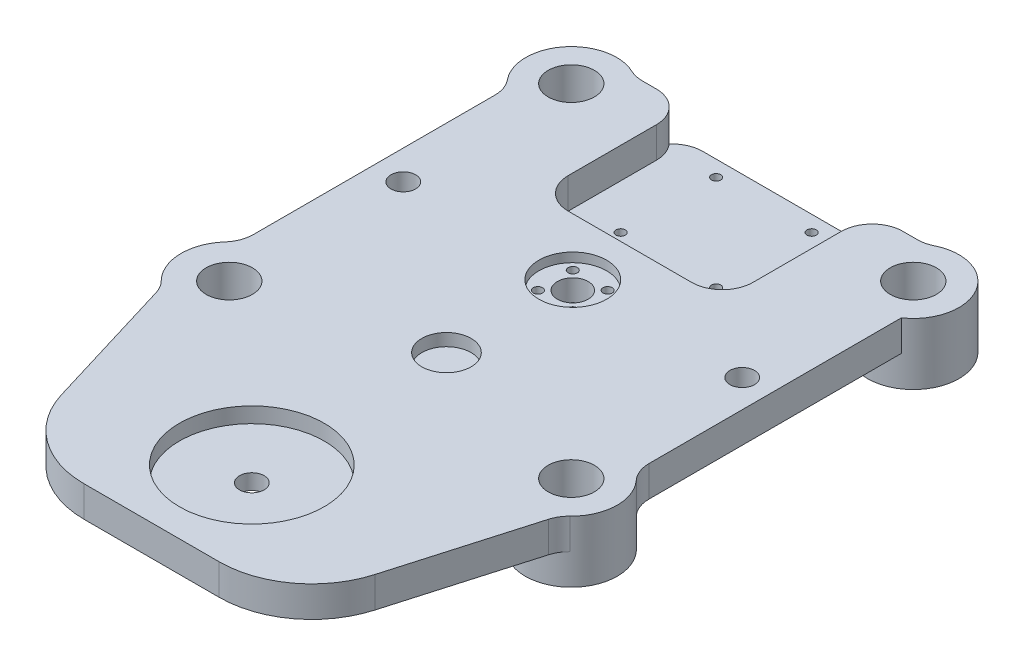
SolidWorks part; units mm, degrees
ref_plane "Front Plane" through (0, 0, 0) normal (0, 0, 1) x (1, 0, 0)
ref_plane "Top Plane" through (0, 0, 0) normal (0, 1, 0) x (1, 0, 0)
ref_plane "Right Plane" through (0, 0, 0) normal (1, 0, 0) x (0, 0, -1)
sketch "Sketch1" plane through (0, 0, 0) normal (0, 1, 0) x (1, 0, 0)
  line L0 (-55.3435, 80.7701) -> (55.6565, 80.7701) construction
  line L1 (-47.2225, 93.074) -> (47.3428, 93.074)
  line L2 (-64.5152, 69.2281) -> (-64.5152, -17.5957)
  line L4 (64.0417, 68.5147) -> (64.0417, -17.8733)
  line L5 (0.1565, -45.5027) -> (0.1565, -78.0027) construction
  line L6 (0.1565, -78.0027) -> (0.1565, -110.7506) construction
  line L7 (55.6565, 80.7701) -> (55.6565, -30.2299) construction
  line L8 (-55.3435, 80.7701) -> (-55.3435, -30.2299) construction
  line L9 (-55.3435, -30.2299) -> (55.6565, -30.2299) construction
  line L15 (-55.3435, -45.8423) -> (55.6565, -45.1631) construction
  line L20 (-44.1665, -110.7506) -> (44.4795, -110.7506)
  line L21 (-64.7902, -42.6599) -> (-44.1665, -110.7506)
  line L22 (44.4795, -110.7506) -> (64.2297, -42.4569)
  arc A0 (-47.2225, 93.074) -> (-64.5152, 69.2281) centre (-55.3435, 80.7701) ccw
  arc A1 (64.0417, 68.5147) -> (47.3428, 93.074) centre (55.6565, 80.7701) ccw
  circle A2 centre (-55.3435, 80.7701) radius 7.5
  circle A3 centre (55.6565, 80.7701) radius 7.5
  arc A4 (-64.5152, -17.5957) -> (-64.7902, -42.6599) centre (-55.3435, -30.2299) ccw
  arc A5 (64.2297, -42.4569) -> (64.0417, -17.8733) centre (55.6565, -30.2299) ccw
  circle A6 centre (-55.3435, -30.2299) radius 7.5
  circle A7 centre (55.6565, -30.2299) radius 7.5
  arc A9 (-64.7902, -42.6599) -> (-64.5152, -17.5957) centre (-55.3435, -30.2299) ccw construction
  arc A10 (64.0417, -17.8733) -> (64.2297, -42.4569) centre (55.6565, -30.2299) ccw construction
  point P0 (0, 0)
  point P29 (0.1565, -110.7506)
extrude "Boss-Extrude1" add sketch "Sketch1" along normal blind 20
sketch "Sketch2" plane through (0, 20, 0) normal (0, 1, 0) x (1, 0, 0)
  line L1 (-15.5, 87.9354) -> (15.5, 87.9354) construction
  line L2 (-15.5, 87.9354) -> (-15.5, 56.9354) construction
  line L3 (-15.5, 56.9354) -> (15.5, 56.9354) construction
  line L4 (15.5, 87.9354) -> (15.5, 56.9354) construction
  line L5 (-15.5, 87.9354) -> (15.5, 56.9354) construction
  line L6 (-15.5, 56.9354) -> (15.5, 87.9354) construction
  circle A0 centre (-15.5, 87.9354) radius 1.5
  circle A1 centre (15.5, 87.9354) radius 1.5
  circle A2 centre (-15.5, 56.9354) radius 1.5
  circle A3 centre (15.5, 56.9354) radius 1.5
  point P0 (0, 72.4354)
extrude "Cut-Extrude1" cut sketch "Sketch2" against normal blind 20
sketch "Sketch4" plane through (0, 20, 0) normal (0, 1, 0) x (1, 0, 0)
  line L1 (-55.3435, 80.7701) -> (55.6565, 80.7701) construction
  line L2 (-55.3435, 80.7701) -> (-55.3435, -30.2299) construction
  line L3 (-55.3435, -30.2299) -> (55.6565, -30.2299) construction
  line L4 (55.6565, 80.7701) -> (55.6565, -30.2299) construction
  circle A0 centre (0, 25.9114) radius 5
extrude "Cut-Extrude2" cut sketch "Sketch4" against normal blind 20
sketch "Sketch5" plane through (0, 20, 0) normal (0, 1, 0) x (1, 0, 0)
  circle A0 centre (0, 25.9114) radius 11
extrude "Cut-Extrude3" cut sketch "Sketch5" against normal blind 3
sketch "Sketch6" plane through (0, 17, 0) normal (0, 1, 0) x (1, 0, 0)
  line L1 (-5.6569, 31.5682) -> (5.6569, 31.5682) construction
  line L2 (-5.6569, 31.5682) -> (-5.6569, 20.2545) construction
  line L3 (-5.6569, 20.2545) -> (5.6569, 20.2545) construction
  line L4 (5.6569, 31.5682) -> (5.6569, 20.2545) construction
  line L5 (-5.6569, 31.5682) -> (5.6569, 20.2545) construction
  line L6 (-5.6569, 20.2545) -> (5.6569, 31.5682) construction
  circle A0 centre (-5.6569, 31.5682) radius 1.5
  circle A1 centre (5.6569, 31.5682) radius 1.5
  circle A2 centre (5.6569, 20.2545) radius 1.5
  circle A3 centre (-5.6569, 20.2545) radius 1.5
  point P0 (0, 25.9114)
extrude "Cut-Extrude4" cut sketch "Sketch6" against normal through all
sketch "Sketch7" plane through (0, 20, 0) normal (0, 1, 0) x (1, 0, 0)
  circle A0 centre (0, -15.077) radius 8
extrude "Cut-Extrude5" cut sketch "Sketch7" against normal blind 4
fillet "Fillet3" radius 30 2 edges at (44.4795, 10, 110.7506) (-44.1665, 10, 110.7506)
fillet "Fillet4" radius 10 2 edges at (64.2297, 10, 42.4569) (-64.7902, 10, 42.6599)
sketch "Sketch9" plane through (0, 20, 0) normal (0, 1, 0) x (1, 0, 0)
  line L0 (-21.9072, -110.7506) -> (21.926, -110.7506) construction
  circle A0 centre (0, -78.2506) radius 23.5
  dimension "D1" = 32.5
extrude "Cut-Extrude6" cut sketch "Sketch9" against normal blind 5
sketch "Sketch10" plane through (0, 15, 0) normal (0, 1, 0) x (1, 0, 0)
  circle A0 centre (0, -78.2506) radius 4
extrude "Cut-Extrude7" cut sketch "Sketch10" against normal through all
sketch "Sketch11" plane through (0, 20, 0) normal (0, 1, 0) x (1, 0, 0)
  line L0 (-30, 44.4354) -> (30, 44.4354)
  line L1 (-15.5, 56.9354) -> (15.5, 87.9354) construction
  line L2 (-30, 44.4354) -> (-30, 114.4354)
  line L3 (-30, 114.4354) -> (30, 114.4354)
  line L4 (30, 114.4354) -> (30, 44.4354)
  point P3 (0, 44.4354)
  point P8 (0, 72.4354)
  dimension "D1" = 28
extrude "Cut-Extrude8" cut sketch "Sketch11" against normal blind 10
fillet "Fillet5" radius 10 2 edges at (30, 15, -44.4354) (-30, 15, -44.4354)
sketch "Sketch12" plane through (0, 0, 0) normal (0, -1, 0) x (1, 0, 0)
  line L0 (-55, -25.9114) -> (55, -25.9114) construction
  circle A0 centre (-55, -25.9114) radius 4 construction
  circle A1 centre (55, -25.9114) radius 4 construction
  circle A2 centre (-55, -25.9114) radius 12
  circle A3 centre (55, -25.9114) radius 12
  point P4 (0, -25.9114)
extrude "Cut-Extrude9" cut sketch "Sketch12" against normal blind 10
fillet "Fillet6" radius 10 4 edges at (64.0417, 5, -33.801) (64.0417, 5, -18.0217) (-64.5152, 5, -33.2231) (-64.5152, 5, -18.5997)
sketch "Sketch13" plane through (0, 10, 0) normal (0, -1, 0) x (1, 0, 0)
  circle A0 centre (-55, -25.9114) radius 4
  circle A1 centre (55, -25.9114) radius 4
extrude "Cut-Extrude10" cut sketch "Sketch13" against normal through all
sketch "Sketch14" plane through (0, 0, 0) normal (0, -1, 0) x (1, 0, 0)
  line L0 (-15.5, -56.9354) -> (15.5, -87.9354) construction
  line L1 (-35, -39.4354) -> (35, -39.4354)
  line L2 (-35, -39.4354) -> (-35, -93.074)
  line L3 (35, -93.074) -> (47.3428, -93.074)
  line L4 (-16.9351, -101.3096) -> (-16.7194, -101.3096)
  line L5 (35, -39.4354) -> (35, -93.074)
  line L8 (64.0417, -68.5147) -> (64.0417, -47.8905)
  line L9 (64.0417, -3.9323) -> (64.0417, 17.8733)
  line L10 (63.3869, 45.371) -> (50.7451, 89.0849)
  line L11 (21.926, 110.7506) -> (-21.9072, 110.7506)
  line L12 (-50.6191, 89.447) -> (-63.9757, 45.3491)
  line L13 (-64.5152, 17.5957) -> (-64.5152, -3.9167)
  line L14 (-64.5152, -47.906) -> (-64.5152, -69.2281)
  line L15 (-47.2225, -93.074) -> (47.3428, -93.074)
  line L16 (64.0417, -68.5147) -> (64.0417, -47.8905)
  line L17 (64.0417, -3.9323) -> (64.0417, 17.8733)
  line L18 (63.3869, 45.371) -> (50.7451, 89.0849)
  line L19 (21.926, 110.7506) -> (-21.9072, 110.7506)
  line L20 (-50.6191, 89.447) -> (-63.9757, 45.3491)
  line L21 (-64.5152, 17.5957) -> (-64.5152, -3.9167)
  line L22 (-64.5152, -47.906) -> (-64.5152, -69.2281)
  line L23 (-47.2225, -93.074) -> (-35, -93.074)
  arc A0 (-64.5152, 17.5957) -> (-66.4393, 41.213) centre (-55.3435, 30.2299) ccw
  arc A1 (66.04, 40.9622) -> (64.0417, 17.8733) centre (55.6565, 30.2299) ccw
  arc A2 (-47.2225, -93.074) -> (-64.5152, -69.2281) centre (-55.3435, -80.7701) ccw
  arc A3 (64.0417, -68.5147) -> (47.3428, -93.074) centre (55.6565, -80.7701) ccw
  arc A14 (64.0417, -47.8905) -> (54.4773, -37.9) centre (54.0417, -47.8905) ccw
  arc A15 (54.4773, -13.9228) -> (54.4773, -37.9) centre (55, -25.9114) ccw
  arc A16 (54.4773, -13.9228) -> (64.0417, -3.9323) centre (54.0417, -3.9323) ccw
  arc A17 (64.0417, 17.8733) -> (66.04, 40.9622) centre (55.6565, 30.2299) ccw
  arc A18 (63.3869, 45.371) -> (66.04, 40.9622) centre (72.9933, 48.1491) ccw
  arc A19 (50.7451, 89.0849) -> (21.926, 110.7506) centre (21.926, 80.7506) ccw
  arc A20 (-21.9072, 110.7506) -> (-50.6191, 89.447) centre (-21.9072, 80.7506) ccw
  arc A21 (-66.4393, 41.213) -> (-63.9757, 45.3491) centre (-73.5463, 48.2479) ccw
  arc A22 (-66.4393, 41.213) -> (-64.5152, 17.5957) centre (-55.3435, 30.2299) ccw
  arc A23 (-64.5152, -3.9167) -> (-54.7356, -13.9143) centre (-54.5152, -3.9167) ccw
  arc A24 (-54.7356, -37.9085) -> (-54.7356, -13.9143) centre (-55, -25.9114) ccw
  arc A25 (-54.7356, -37.9085) -> (-64.5152, -47.906) centre (-54.5152, -47.906) ccw
  arc A26 (-64.5152, -69.2281) -> (-47.2225, -93.074) centre (-55.3435, -80.7701) ccw
  arc A27 (47.3428, -93.074) -> (64.0417, -68.5147) centre (55.6565, -80.7701) ccw
  arc A28 (64.0417, -47.8905) -> (54.4773, -37.9) centre (54.0417, -47.8905) ccw
  arc A29 (54.4773, -13.9228) -> (54.4773, -37.9) centre (55, -25.9114) ccw
  arc A30 (54.4773, -13.9228) -> (64.0417, -3.9323) centre (54.0417, -3.9323) ccw
  arc A31 (64.0417, 17.8733) -> (66.04, 40.9622) centre (55.6565, 30.2299) ccw
  arc A32 (63.3869, 45.371) -> (66.04, 40.9622) centre (72.9933, 48.1491) ccw
  arc A33 (50.7451, 89.0849) -> (21.926, 110.7506) centre (21.926, 80.7506) ccw
  arc A34 (-21.9072, 110.7506) -> (-50.6191, 89.447) centre (-21.9072, 80.7506) ccw
  arc A35 (-66.4393, 41.213) -> (-63.9757, 45.3491) centre (-73.5463, 48.2479) ccw
  arc A37 (-64.5152, -3.9167) -> (-54.7356, -13.9143) centre (-54.5152, -3.9167) ccw
  arc A38 (-54.7356, -37.9085) -> (-54.7356, -13.9143) centre (-55, -25.9114) ccw
  arc A39 (-54.7356, -37.9085) -> (-64.5152, -47.906) centre (-54.5152, -47.906) ccw
  arc A41 (47.3428, -93.074) -> (64.0417, -68.5147) centre (55.6565, -80.7701) ccw
  point P21 (0, -39.4354)
  point P26 (0, -72.4354)
  circle M27 centre (0, 78.2506) radius 4
  circle M28 centre (-5.6569, -20.2545) radius 1.5
  circle M29 centre (5.6569, -20.2545) radius 1.5
  circle M30 centre (5.6569, -31.5682) radius 1.5
  circle M31 centre (-5.6569, -31.5682) radius 1.5
  circle M32 centre (0, -25.9114) radius 5
  line M37 (64.0417, -68.5147) -> (64.0417, -47.8905)
  arc M38 (64.0417, -47.8905) -> (54.4773, -37.9) centre (54.0417, -47.8905) ccw
  arc M39 (54.4773, -37.9) -> (54.4773, -13.9228) centre (55, -25.9114) cw
  arc M40 (54.4773, -13.9228) -> (64.0417, -3.9323) centre (54.0417, -3.9323) ccw
  line M41 (64.0417, -3.9323) -> (64.0417, 17.8733)
  arc M43 (66.04, 40.9622) -> (63.3869, 45.371) centre (72.9933, 48.1491) cw
  line M44 (63.3869, 45.371) -> (50.7451, 89.0849)
  arc M45 (50.7451, 89.0849) -> (21.926, 110.7506) centre (21.926, 80.7506) ccw
  line M46 (21.926, 110.7506) -> (-21.9072, 110.7506)
  arc M47 (-21.9072, 110.7506) -> (-50.6191, 89.447) centre (-21.9072, 80.7506) ccw
  line M48 (-50.6191, 89.447) -> (-63.9757, 45.3491)
  arc M49 (-63.9757, 45.3491) -> (-66.4393, 41.213) centre (-73.5463, 48.2479) cw
  line M51 (-64.5152, 17.5957) -> (-64.5152, -3.9167)
  arc M52 (-64.5152, -3.9167) -> (-54.7356, -13.9143) centre (-54.5152, -3.9167) ccw
  arc M53 (-54.7356, -13.9143) -> (-54.7356, -37.9085) centre (-55, -25.9114) cw
  arc M54 (-54.7356, -37.9085) -> (-64.5152, -47.906) centre (-54.5152, -47.906) ccw
  line M55 (-64.5152, -47.906) -> (-64.5152, -69.2281)
  line M57 (-47.2225, -93.074) -> (47.3428, -93.074)
  dimension "D2" = 33
  dimension "D1" = 0
extrude "Cut-Extrude11" cut sketch "Sketch14" against normal blind 10 contours A3 A1 A0 A2 L2 L1 L5 M37 M38 M39 M40 M41 M43 M44 M45 M46 M47 M48 M49 M51 M52 M53 M54 M55 M57 M27 M29 M31 M32 M30 M28 region at (-0.0024, 0, 24.0045)
fillet "Fillet8" radius 10 9 edges at (-64.5152, 15, 17.5957) (64.0417, 15, 17.8733) (35, 5, -39.4354) (-35, 5, -39.4354) (-64.5152, 15, -69.2281) (-47.2225, 15, -93.074) (-30, 15, -93.074) (30, 15, -93.074) (47.3428, 15, -93.074)
fillet "Fillet9" radius 10 2 edges at (-35, 5, -93.074) (35, 5, -93.074)
